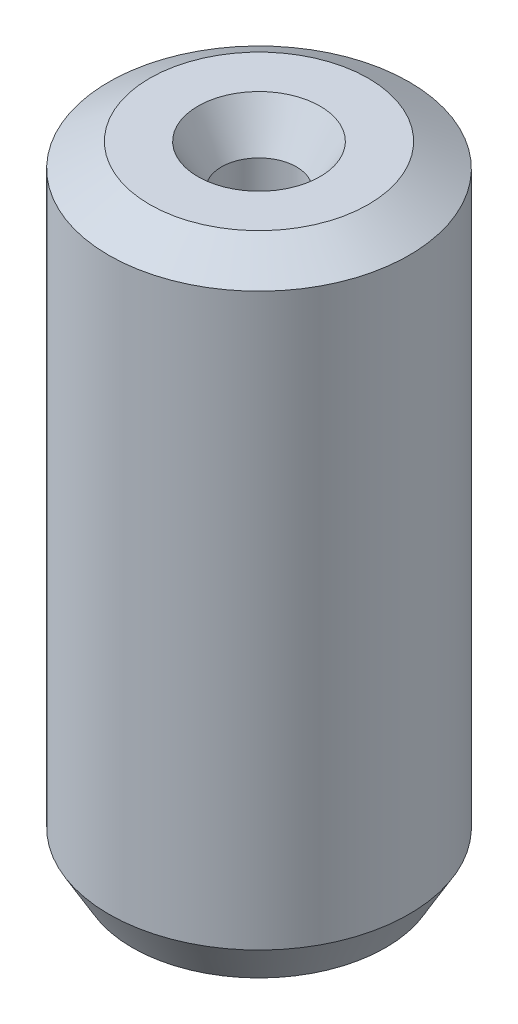
SolidWorks part; units mm, degrees
ref_plane "Front Plane" through (0, 0, 0) normal (0, 0, 1) x (1, 0, 0)
ref_plane "Top Plane" through (0, 0, 0) normal (0, 1, 0) x (1, 0, 0)
ref_plane "Right Plane" through (0, 0, 0) normal (1, 0, 0) x (0, 0, -1)
sketch "Sketch1" plane through (0, 0, 0) normal (0, 1, 0) x (1, 0, 0)
  circle A0 centre (0, 0) radius 5
  dimension "SLEEVE_OD" = 10
extrude "Boss-Extrude1" add sketch "Sketch1" along normal blind 21.1404
sketch "Sketch2" plane through (0, 0, 0) normal (0, 1, 0) x (1, 0, 0)
  circle A0 centre (0, 0) radius 1.2495
  dimension "BORE_D" = 2.499
extrude "Cut-Extrude1" cut sketch "Sketch2" along normal through all
chamfer "Chamfer1" distance 0.7847 angle 60 4 edges at (0, 21.1404, 1.2495) (0, 0, 1.2495) (0, 0, 5) (0, 21.1404, 5) first distance on face at (0, 21.1404, 1.2495) first distance on face at (0, 0, 1.2495) first distance on face at (0, 21.1404, 5)
